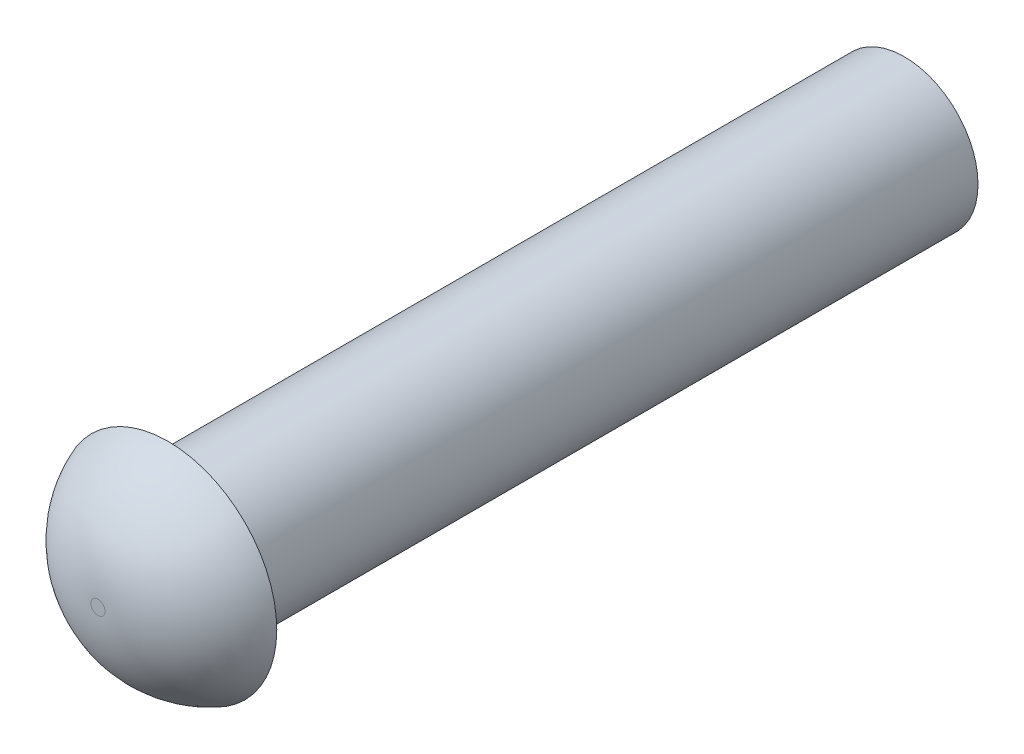
SolidWorks part; units mm, degrees
ref_plane "Płaszczyzna przednia" through (0, 0, 0) normal (0, 0, 1) x (1, 0, 0)
ref_plane "Płaszczyzna górna" through (0, 0, 0) normal (0, 1, 0) x (1, 0, 0)
ref_plane "Płaszczyzna prawa" through (0, 0, 0) normal (1, 0, 0) x (0, 0, -1)
sketch "Szkic1" plane through (0, 0, 0) normal (0, 0, 1) x (1, 0, 0)
  circle A0 centre (0, 0) radius 1.05
  dimension "D1" = 2.1
extrude "Dodanie-wyciągnięcie1" add sketch "Szkic1" along normal blind 6.5 and the other way blind 4
sketch "Szkic2" plane through (0, 0, 6.5) normal (0, 0, 1) x (1, 0, 0)
  circle A0 centre (0, 0) radius 1.55
  dimension "D1" = 3.1
extrude "Dodanie-wyciągnięcie2" add sketch "Szkic2" along normal blind 1
fillet "Zaokrąglenie1" radius 1.55 1 edges at (1.55, 0, 7.5)
